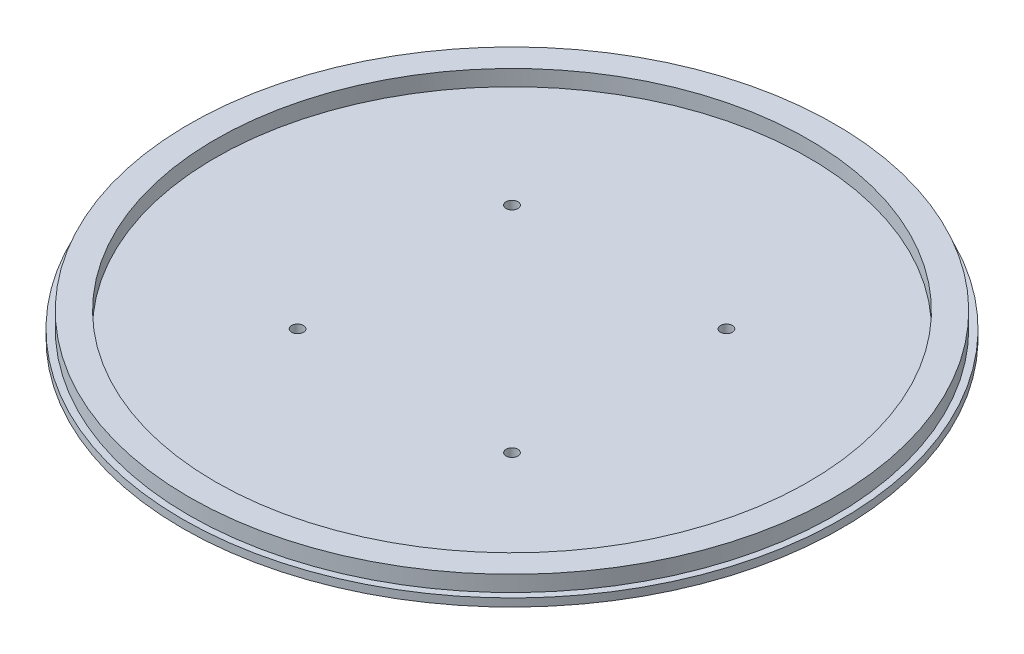
SolidWorks part; units mm, degrees
material "6061-T6 (SS)"
ref_plane "Front Plane" through (0, 0, 0) normal (0, 0, 1) x (1, 0, 0)
ref_plane "Top Plane" through (0, 0, 0) normal (0, 1, 0) x (1, 0, 0)
ref_plane "Right Plane" through (0, 0, 0) normal (1, 0, 0) x (0, 0, -1)
sketch "Sketch1" plane through (0, 0, 0) normal (0, 1, 0) x (1, 0, 0)
  line L0 (-178.7173, 0) -> (178.7173, 0) construction
  line L1 (-55, 0) -> (55, 0) construction
  line L2 (0, 154.67) -> (0, -154.67) construction
  circle A0 centre (0, 0) radius 125
  circle A1 centre (0, 0) radius 60 construction
  point P9 (0, 0)
  point P12 (0, 0)
  dimension "D1" = 250
  dimension "D2" = 120
extrude "Boss-Extrude1" add sketch "Sketch1" along normal blind 3 contours A0
sketch "Sketch2" plane through (0, 3, 0) normal (0, 1, 0) x (1, 0, 0)
  circle A0 centre (0, 0) radius 122.5
  circle A1 centre (0, 0) radius 112.5
  dimension "D1" = 245
  dimension "D2" = 225
extrude "Boss-Extrude2" add sketch "Sketch2" along normal blind 6
sketch "Sketch3" plane through (0, 0, 0) normal (0, -1, 0) x (1, 0, 0)
  line L1 (-47.25, 47.25) -> (47.25, 47.25)
  line L2 (-47.25, 47.25) -> (-47.25, -47.25)
  line L3 (-47.25, -47.25) -> (47.25, -47.25)
  line L4 (47.25, 47.25) -> (47.25, -47.25)
  line L5 (-47.25, 47.25) -> (47.25, -47.25) construction
  line L6 (-47.25, -47.25) -> (47.25, 47.25) construction
  point P0 (0, 0)
  dimension "D1" = 94.5
  dimension "D2" = 94.5
extrude "Boss-Extrude3" add sketch "Sketch3" along normal blind 8 contours L2 L1 L4 L3
sketch "Sketch4" plane through (0, -8, 0) normal (0, -1, 0) x (1, 0, 0)
  line L1 (-40.66, 40.66) -> (40.66, 40.66) construction
  line L2 (-40.66, 40.66) -> (-40.66, -40.66) construction
  line L3 (-40.66, -40.66) -> (40.66, -40.66) construction
  line L4 (40.66, 40.66) -> (40.66, -40.66) construction
  line L5 (-40.66, 40.66) -> (40.66, -40.66) construction
  line L6 (-40.66, -40.66) -> (40.66, 40.66) construction
  circle A1 centre (-40.66, 40.66) radius 3.3
  circle A2 centre (40.66, 40.66) radius 3.3
  circle A3 centre (40.66, -40.66) radius 3.3
  point P0 (0, 0)
  dimension "D1" = 6.6
  dimension "D2" = 81.32
  dimension "D3" = 81.32
hole_wizard "M4 Clearance Hole1" positions "Sketch5" profile "Sketch6" hole size "M4" standard "DIN" end condition through all
sketch "Sketch5" plane through (0, -8, 0) normal (0, -1, 0) x (-1, 0, 0)
  point P0 (40.66, 40.66)
  point P3 (40.66, -40.66)
  point P6 (-40.66, -40.66)
  point P9 (-40.66, 40.66)
sketch "Sketch6" plane through (-40.66, -8, -40.66) normal (1, 0, 0) x (0, 0, -1)
  line L0 (0, 0) -> (0, 17)
  line L1 (0, 17) -> (2.25, 17)
  line L2 (2.25, 17) -> (2.25, 0)
  line L5 (2.25, 0) -> (0, 0)
  line L11 (0, -6.35) -> (0, 107.95) construction
  dimension "Thru Hole Dia." = 4.5
  dimension "Thru Hole Depth" = 17
ref_axis "platecntreaxis" through (0, 133.8451, 0) along (0, -1, 0)
fillet "Fillet1" radius 3 4 edges at (0, 0, -47.25) (47.25, 0, 0) (0, 0, 47.25) (-47.25, 0, 0)
sketch "Sketch7" plane through (0, 0, 0) normal (0, -1, 0) x (1, 0, 0)
  line L0 (0, -9.35) -> (0, 9.35) construction
  line L5 (-12.7859, 101.1901) -> (12.7859, 50.25) construction
  line L6 (-12.7859, 50.25) -> (12.7859, 101.1901) construction
  line L7 (-50.25, 50.25) -> (50.25, 50.25) construction
  point P0 (0, 75.72)
  dimension "D1" = 50.9401
sketch "Sketch8" plane through (0, 0, 0) normal (0, -1, 0) x (-1, 0, 0)
  line L0 (125, 0) -> (75.1, 0) construction
  line L1 (-9.35, 0) -> (9.35, 0) construction
  line L3 (85.6, -10.5) -> (64.6, -10.5)
  line L4 (85.6, -10.5) -> (85.6, 10.5)
  line L5 (85.6, 10.5) -> (64.6, 10.5)
  line L6 (64.6, -10.5) -> (64.6, 10.5)
  line L7 (85.6, -10.5) -> (64.6, 10.5) construction
  line L8 (85.6, 10.5) -> (64.6, -10.5) construction
  circle A0 centre (0, 0) radius 125 construction
  dimension "D1" = 49.9
  dimension "D2" = 21
  dimension "D3" = 21
extrude "Boss-Extrude4" add sketch "Sketch8" along normal blind 5 contours L4 L3 L6 L5
fillet "Fillet2" radius 6 4 edges at (-64.6, 0, 0) (-75.1, 0, 10.5) (-85.6, 0, 0) (-75.1, 0, -10.5)
fillet "Fillet3" radius 23 4 edges at (-85.6, -5, 0) (-75.1, -5, -10.5) (-64.6, -5, 0) (-75.1, -5, 10.5)
